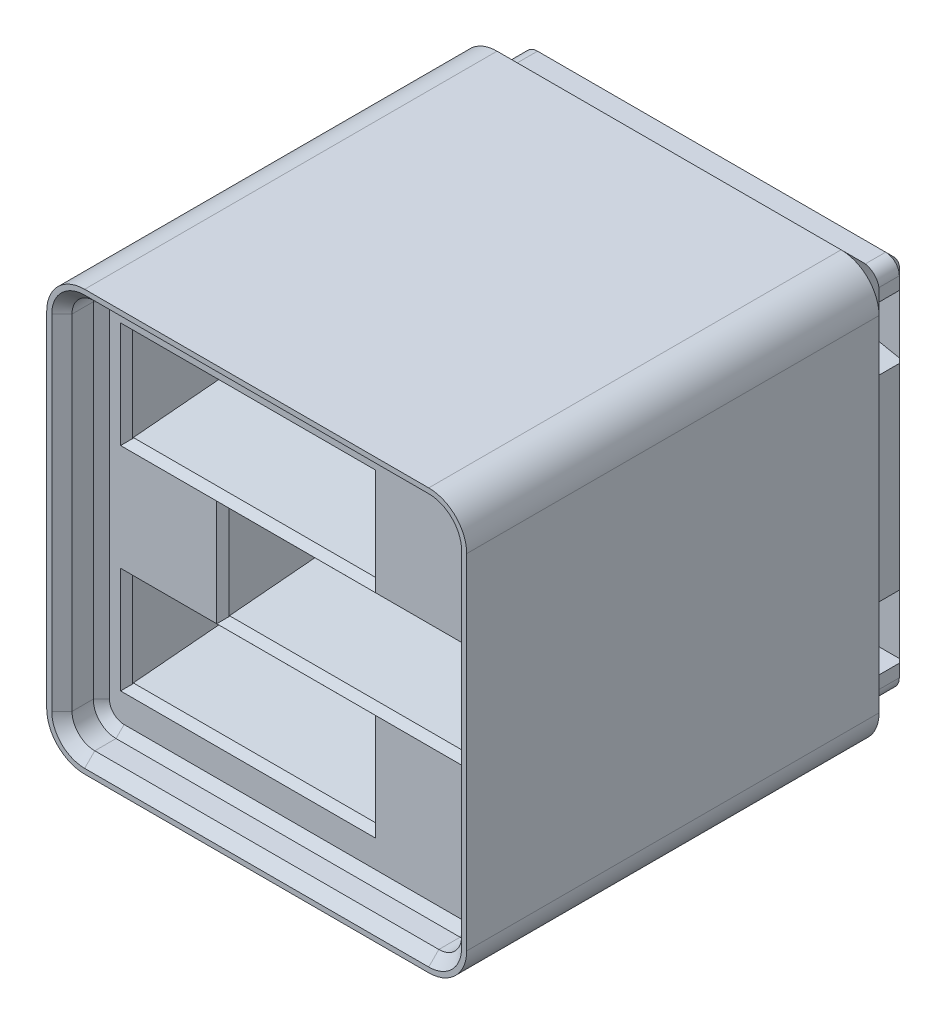
SolidWorks part; units mm, degrees
ref_plane "Front Plane" through (0, 0, 0) normal (0, 0, 1) x (1, 0, 0)
ref_plane "Top Plane" through (0, 0, 0) normal (0, 1, 0) x (1, 0, 0)
ref_plane "Right Plane" through (0, 0, 0) normal (1, 0, 0) x (0, 0, -1)
sketch "Sketch1" plane through (0, 0, 0) normal (0, 0, 1) x (1, 0, 0)
  line L1 (18.55, 18.55) -> (-18.55, 18.55)
  line L2 (18.55, 18.55) -> (18.55, -18.55)
  line L3 (18.55, -18.55) -> (-18.55, -18.55)
  line L4 (-18.55, 18.55) -> (-18.55, -18.55)
  line L5 (18.55, 18.55) -> (-18.55, -18.55) construction
  line L6 (18.55, -18.55) -> (-18.55, 18.55) construction
  point P0 (0, 0)
  dimension "D1" = 37.1
extrude "Boss-Extrude1" add sketch "Sketch1" along normal blind 2.6
sketch "Sketch2" plane through (0, 0, 2.6) normal (0, 0, 1) x (1, 0, 0)
  line L1 (-20.75, 20.75) -> (20.75, 20.75)
  line L2 (-20.75, 20.75) -> (-20.75, -20.75)
  line L3 (-20.75, -20.75) -> (20.75, -20.75)
  line L4 (20.75, 20.75) -> (20.75, -20.75)
  line L5 (-20.75, 20.75) -> (20.75, -20.75) construction
  line L6 (-20.75, -20.75) -> (20.75, 20.75) construction
  point P0 (0, 0)
  dimension "D1" = 41.5
extrude "Boss-Extrude2" add sketch "Sketch2" along normal blind 2.4
sketch "Sketch8" plane through (0, 0, 2.6) normal (0, 0, -1) x (-1, 0, 0)
  line L0 (-18.55, 18.55) -> (-18.55, 5.0094) construction
  line L1 (-18.55, -18.55) -> (-18.55, 18.55) construction
  line L2 (-14.9962, 10.4) -> (-18.55, 9.7)
  line L8 (12.7, 15.95) -> (-12.7, 15.95) construction
  line L9 (12.7, 9.45) -> (-12.7, 9.45) construction
  line L11 (-12.7, 15.95) -> (-18.55, 15.95)
  line L12 (-12.7, 12.7) -> (-12.7, -12.7)
  line L13 (-12.7, -12.7) -> (12.7, -12.7)
  line L14 (12.7, -12.7) -> (12.7, 12.7)
  line L15 (12.7, 12.7) -> (-12.7, 12.7)
  line L16 (-12.7, 9.45) -> (-12.7, -12.7) construction
  line L17 (-12.7, -12.7) -> (12.7, -12.7) construction
  line L18 (12.7, -12.7) -> (12.7, 12.7) construction
  line L19 (12.7, 12.7) -> (-12.7, 12.7) construction
  line L22 (-18.55, 15.95) -> (-18.55, 9.7)
  arc A0 (-12.7, 15.95) -> (-12.7, 9.45) centre (-12.7, 12.7) cw
  arc A1 (-12.7, 9.45) -> (-14.9962, 10.4) centre (-12.7, 12.7) cw
  dimension "D4" = 5.55
  dimension "D5" = 6.25
  dimension "D1" = 8.05
  dimension "D2" = 3.25
  dimension "D3" = 3.25
extrude "Base Magnet Slot" cut sketch "Sketch8" against normal blind 0.4 and the other way blind 2.2
fillet "Fillet1" radius 1.35 4 edges at (18.55, 18.55, 1.3) (18.55, -18.55, 1.3) (-18.55, -18.55, 1.3) (-18.55, 18.55, 1.3)
fillet "Fillet2" radius 3.75 4 edges at (20.75, -20.75, 3.8) (20.75, 20.75, 3.8) (-20.75, -20.75, 3.8) (-20.75, 20.75, 3.8)
chamfer "Chamfer1" distance 0.8 angle 45 8 edges at (-18.1546, 18.1546, 0) (-18.55, 0, 0) (-18.1546, -18.1546, 0) (0, -18.55, 0) (18.1546, -18.1546, 0) (18.55, 0, 0) (18.1546, 18.1546, 0) (0, 18.55, 0)
chamfer "Chamfer2" distance 2.4 angle 45 8 edges at (20.75, 0, 2.6) (19.6517, 19.6517, 2.6) (19.6517, -19.6517, 2.6) (0, 20.75, 2.6) (0, -20.75, 2.6) (-19.6517, 19.6517, 2.6) (-19.6517, -19.6517, 2.6) (-20.75, 0, 2.6)
mirror "Mirror1" about plane through (0, 0, 0) normal (0, 1, 0) of "Base Magnet Slot"
mirror "Mirror2" about plane through (0, 0, 0) normal (1, 0, 0) of "Mirror1"
sketch "Sketch14" plane through (0, 0, 0) normal (0, 0, -1) x (-1, 0, 0)
  line L0 (17.2, 17.75) -> (-17.2, 17.75) construction
  line L1 (-3, -15.75) -> (3, -15.75)
  line L2 (-3, -15.75) -> (-3, -3)
  line L3 (-3, 15.75) -> (3, 15.75)
  line L4 (3, -15.75) -> (3, -3)
  line L5 (-3, -15.75) -> (3, 15.75) construction
  line L6 (-3, 15.75) -> (3, -15.75) construction
  line L7 (-17.75, 17.2) -> (-17.75, -17.2) construction
  line L8 (-15.75, 3) -> (-3, 3)
  line L9 (-15.75, 3) -> (-15.75, -3)
  line L10 (-15.75, -3) -> (-3, -3)
  line L11 (15.75, 3) -> (15.75, -3)
  line L12 (-15.75, 3) -> (15.75, -3) construction
  line L13 (-15.75, -3) -> (15.75, 3) construction
  line L14 (-3, 3) -> (-3, 15.75)
  line L16 (3, 3) -> (15.75, 3)
  line L17 (3, 3) -> (3, 15.75)
  line L19 (3, -3) -> (15.75, -3)
  point P0 (0, 0)
  point P10 (0, 0)
  dimension "D1" = 6
  dimension "D2" = 2
  dimension "D3" = 2
extrude "Cut-Extrude2" cut sketch "Sketch14" against normal blind 3
fillet "Fillet4" radius 1 36 edges at (-9.375, -3, 0) (9.375, -3, 0) (-3, 9.375, 0) (-15.75, 0, 0) (0, -15.75, 0) (15.75, 0, 0) (0, 15.75, 0) (9.375, -3, 3) (-3, -9.375, 3) (-3, 9.375, 3) (3, 9.375, 3) (-9.375, 3, 0) (-3, -9.375, 0) (3, -9.375, 0) (9.375, 3, 0) (3, 9.375, 0) (0, -15.75, 3) (3, -9.375, 3) (3, -3, 1.5) (-15.75, 0, 3) (-9.375, -3, 3) (-9.375, 3, 3) (0, 15.75, 3) (9.375, 3, 3) (15.75, 0, 3) (-3, -3, 1.5) (-3, 3, 1.5) (3, 3, 1.5) (-15.75, 3, 1.5) (-15.75, -3, 1.5) (-3, -15.75, 1.5) (3, -15.75, 1.5) (15.75, -3, 1.5) (-3, 15.75, 1.5) (3, 15.75, 1.5) (15.75, 3, 1.5)
sketch "Sketch15" plane through (0, 0, 5) normal (0, 0, 1) x (1, 0, 0)
  line L0 (-20.75, -17) -> (-20.75, 17)
  line L1 (-20.75, -17) -> (-20.75, 17)
  line L2 (-17, 20.75) -> (17, 20.75)
  line L3 (-17, 20.75) -> (17, 20.75)
  line L4 (20.75, 17) -> (20.75, -17)
  line L5 (20.75, 17) -> (20.75, -17)
  line L6 (17, -20.75) -> (-17, -20.75)
  line L7 (17, -20.75) -> (-17, -20.75)
  arc A0 (-20.75, -17) -> (-17, -20.75) centre (-17, -17) ccw
  arc A1 (-20.75, -17) -> (-17, -20.75) centre (-17, -17) ccw
  arc A2 (-17, 20.75) -> (-20.75, 17) centre (-17, 17) ccw
  arc A3 (-17, 20.75) -> (-20.75, 17) centre (-17, 17) ccw
  arc A4 (20.75, 17) -> (17, 20.75) centre (17, 17) ccw
  arc A5 (20.75, 17) -> (17, 20.75) centre (17, 17) ccw
  arc A6 (17, -20.75) -> (20.75, -17) centre (17, -17) ccw
  arc A7 (17, -20.75) -> (20.75, -17) centre (17, -17) ccw
extrude "Boss-Extrude3" add sketch "Sketch15" along normal blind 36.85
sketch "Sketch16" plane through (0, 0, 41.85) normal (0, 0, 1) x (1, 0, 0)
  line L0 (-20.75, 0) -> (20.75, 0) construction
  line L1 (-20.75, 17) -> (-20.75, -17) construction
  line L2 (20.75, -17) -> (20.75, 17) construction
  line L3 (-20.75, -10.5) -> (20.75, -10.5) construction
  line L4 (-20.75, 10.5) -> (20.75, 10.5) construction
  line L5 (7.25, -9) -> (7.25, -12)
  line L6 (-16.75, 12) -> (7.25, 12)
  line L7 (-16.75, 12) -> (-16.75, 9)
  line L8 (-16.75, 9) -> (7.25, 9)
  line L9 (7.25, 12) -> (7.25, 9)
  line L10 (-16.75, -9) -> (7.25, -9)
  line L11 (-16.75, -12) -> (7.25, -12)
  line L12 (-16.75, -9) -> (-16.75, -12)
  line L14 (-7.25, 1.5) -> (16.75, 1.5)
  line L15 (-7.25, 1.5) -> (-7.25, -1.5)
  line L16 (-7.25, -1.5) -> (16.75, -1.5)
  line L17 (16.75, 1.5) -> (16.75, -1.5)
  point P18 (-16.75, 10.5)
  point P23 (-7.0562, -1.5202)
  point P24 (-7.8594, 1.9218)
  point P25 (16.75, 0)
  dimension "D1" = 10.5
  dimension "D3" = 3
  dimension "D4" = 24
  dimension "D5" = 4
  dimension "D6" = 4
  dimension "D2" = 10.5
extrude "Cut-Extrude3" cut sketch "Sketch16" against normal blind 36
draft "Draft1" type of draft neutral plane draft angle 5 faces to draft 6 face at (4.75, -1.5, 23.85) face at (4.75, 1.5, 23.85) face at (-4.75, -12, 23.85) face at (-4.75, -9, 23.85) face at (-4.75, 9, 23.85) face at (-4.75, 12, 23.85) neutral plane through (0, 0, 5.85) neutral plane normal (0, 0, 1) parameters "D1"=5
sketch "Sketch17" plane through (0, 0, 41.85) normal (0, 0, 1) x (1, 0, 0)
  line L0 (-17, -20.75) -> (17, -20.75) construction
  line L1 (20.75, -17) -> (20.75, 17) construction
  line L2 (17, 20.75) -> (-17, 20.75) construction
  line L3 (-20.75, 17) -> (-20.75, -17) construction
  line L4 (-17, -20.75) -> (17, -20.75)
  line L5 (20.75, -17) -> (20.75, 17)
  line L6 (17, 20.75) -> (-17, 20.75)
  line L7 (-20.75, 17) -> (-20.75, -17)
  line L8 (-17, -19.25) -> (17, -19.25)
  line L9 (19.25, -17) -> (19.25, 17)
  line L10 (17, 19.25) -> (-17, 19.25)
  line L11 (-19.25, 17) -> (-19.25, -17)
  arc A0 (-20.75, -17) -> (-17, -20.75) centre (-17, -17) ccw construction
  arc A1 (17, -20.75) -> (20.75, -17) centre (17, -17) ccw construction
  arc A2 (20.75, 17) -> (17, 20.75) centre (17, 17) ccw construction
  arc A3 (-17, 20.75) -> (-20.75, 17) centre (-17, 17) ccw construction
  arc A4 (-20.75, -17) -> (-17, -20.75) centre (-17, -17) ccw
  arc A5 (17, -20.75) -> (20.75, -17) centre (17, -17) ccw
  arc A6 (20.75, 17) -> (17, 20.75) centre (17, 17) ccw
  arc A7 (-17, 20.75) -> (-20.75, 17) centre (-17, 17) ccw
  arc A8 (17, -19.25) -> (19.25, -17) centre (17, -17) ccw
  arc A9 (19.25, 17) -> (17, 19.25) centre (17, 17) ccw
  arc A10 (-17, 19.25) -> (-19.25, 17) centre (-17, 17) ccw
  arc A11 (-19.25, -17) -> (-17, -19.25) centre (-17, -17) ccw
  dimension "D1" = 1.5
extrude "Boss-Extrude4" add sketch "Sketch17" along normal blind 3.9
chamfer "Chamfer3" distance 0.8 angle 45 8 edges at (0, -19.25, 41.85) (18.591, -18.591, 41.85) (-18.591, -18.591, 41.85) (19.25, 0, 41.85) (-19.25, 0, 41.85) (18.591, 18.591, 41.85) (-18.591, 18.591, 41.85) (0, 19.25, 41.85)
chamfer "Chamfer4" distance 1 angle 45 8 edges at (0, -19.25, 45.75) (18.591, -18.591, 45.75) (-18.591, -18.591, 45.75) (19.25, 0, 45.75) (-19.25, 0, 45.75) (18.591, 18.591, 45.75) (-18.591, 18.591, 45.75) (0, 19.25, 45.75)
chamfer "Chamfer5" distance 0.6 angle 45 12 edges at (-4.75, -15.1496, 41.85) (7.25, -10.5, 41.85) (-4.75, -5.8504, 41.85) (-16.75, -10.5, 41.85) (4.75, -4.6496, 41.85) (16.75, 0, 41.85) (4.75, 4.6496, 41.85) (-7.25, 0, 41.85) (-4.75, 5.8504, 41.85) (7.25, 10.5, 41.85) (-4.75, 15.1496, 41.85) (-16.75, 10.5, 41.85) first distance on face at (0, 0, 41.85)
